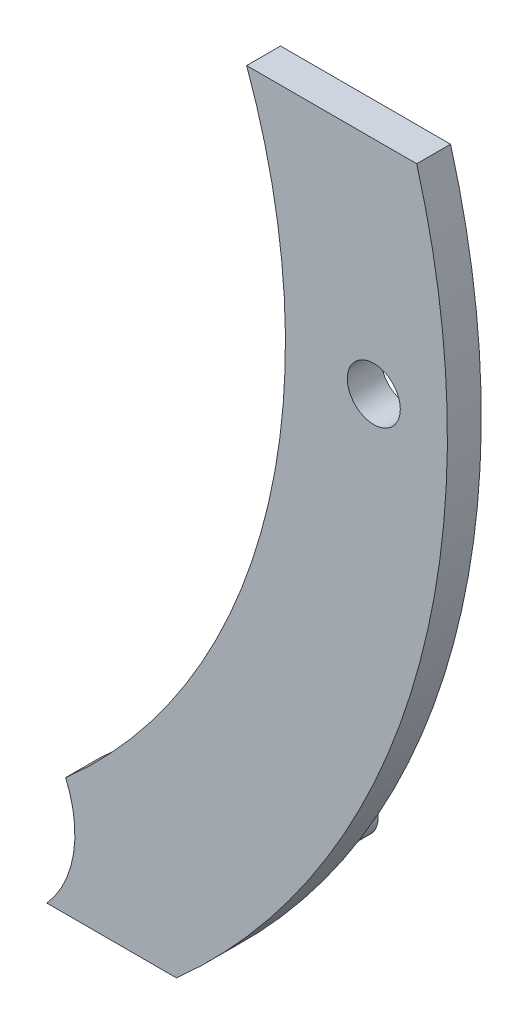
SolidWorks part; units mm, degrees
ref_plane "Front Plane" through (0, 0, 0) normal (0, 0, 1) x (1, 0, 0)
ref_plane "Top Plane" through (0, 0, 0) normal (0, 1, 0) x (1, 0, 0)
ref_plane "Right Plane" through (0, 0, 0) normal (1, 0, 0) x (0, 0, -1)
sketch "Sketch1" plane through (0, 0, 0) normal (0, 0, 1) x (1, 0, 0)
  line L0 (0, 125.7009) -> (0, -111.3832) construction
  line L1 (-141.6644, 0) -> (118.483, 0) construction
  line L2 (0, 69.25) -> (-7.7782, 77.0282) construction
  line L5 (69.0973, -18.82) -> (54.0578, -10.137)
  line L8 (-69.0973, -18.82) -> (-53.8993, -10.9483)
  line L11 (19.8875, 69.25) -> (-21.4021, 69.25) construction
  line L12 (-18.25, 69.25) -> (-18.25, 51.8839)
  line L14 (18.25, 69.25) -> (18.25, 51.8839)
  arc A0 (-75.7772, -43.75) -> (75.7772, -43.75) centre (0, 0) ccw
  circle A18 centre (-7.7782, 77.0282) radius 2.15
  arc A31 (-18.25, 51.8839) -> (-53.8993, -10.9483) centre (0, 0) ccw
  circle A32 centre (0, 0) radius 35
  arc A33 (75.7772, -43.75) -> (69.0973, -18.82) centre (59.9723, -34.625) ccw
  arc A34 (-69.0973, -18.82) -> (-75.7772, -43.75) centre (-59.9723, -34.625) ccw
  arc A36 (54.0578, -10.137) -> (18.25, 51.8839) centre (0, 0) ccw
  circle A38 centre (-50, 0) radius 1.8
  circle A39 centre (-25, 43.3013) radius 1.8
  circle A40 centre (25, 43.3013) radius 1.8
  circle A41 centre (50, 0) radius 1.8
  circle A42 centre (25, -43.3013) radius 1.8
  circle A43 centre (-25, -43.3013) radius 1.8
  arc A44 (18.25, 69.25) -> (-18.25, 69.25) centre (0, 69.25) ccw
  circle A45 centre (7.7782, 77.0282) radius 2.15
  circle A46 centre (7.7782, 61.4718) radius 2.15
  circle A47 centre (-7.7782, 61.4718) radius 2.15
  circle A49 centre (62.8193, -45.2502) radius 2.15
  circle A50 centre (49.3471, -37.472) radius 2.15
  circle A51 centre (57.1252, -23.9998) radius 2.15
  circle A52 centre (70.5974, -31.778) radius 2.15
  circle A54 centre (-70.5974, -31.778) radius 2.15
  circle A55 centre (-57.1252, -23.9998) radius 2.15
  circle A56 centre (-49.3471, -37.472) radius 2.15
  circle A57 centre (-62.8193, -45.2502) radius 2.15
  circle A58 centre (0, 69.25) radius 7.575
  circle A59 centre (59.9723, -34.625) radius 7.575
  circle A60 centre (-59.9723, -34.625) radius 7.575
  point P21 (0, 72.5)
  point P28 (0, 69.25)
  point P40 (0, 0)
  point P41 (0, 0)
  point P42 (0, 72.5)
  point P44 (0, 0)
  point P59 (0, 0)
  point P73 (0, 0)
  point P78 (0, 0)
  dimension "D1" = 175
  dimension "D2" = 70
  dimension "D3" = 18.25
  dimension "D4" = 15.15
  dimension "D5" = 4.3
  dimension "D6" = 11
  dimension "D7" = 3
  dimension "D12" = 110
  dimension "D13" = 3.6
  dimension "D11" = 69.25
  dimension "D8" = 50
  dimension "D15" = 6
  dimension "D9" = 4
  dimension "D10" = 3
extrude "Boss-Extrude1" add sketch "Sketch1" along normal blind 3.175
sketch "Sketch2" plane through (0, 0, 3.175) normal (0, 0, 1) x (1, 0, 0)
  line L0 (0, 93.7487) -> (0, -92.817) construction
  line L1 (-91.7689, 0) -> (95.9614, 0) construction
  line L2 (-35.5093, -64) -> (51.1666, -64) construction
  line L3 (-24, -49) -> (32, -49)
  line L4 (-24, -49) -> (-24, -79)
  line L5 (-24, -79) -> (32, -79)
  line L6 (32, -49) -> (32, -79)
  line L7 (-23.1064, -11.067) -> (5.3725, -70.527)
  line L8 (21.835, -39.1033) -> (32.0072, -56.3108)
  line L9 (0, 0) -> (-23.1064, -11.067) construction
  line L10 (0, 0) -> (25.3854, -3.459) construction
  line L11 (5.3725, -70.527) -> (19, -64) construction
  line L12 (19, -64) -> (32.0072, -56.3108) construction
  line L13 (-19.7204, -33) -> (34.8807, -33) construction
  line L14 (27, -18.9627) -> (27, -48.8294) construction
  line L15 (21, -34.3) -> (39, -34.3)
  line L16 (21, -34.3) -> (21, -37.8)
  line L17 (21, -37.8) -> (39, -37.8)
  line L18 (39, -34.3) -> (39, -37.8)
  line L19 (20.4704, -36.05) -> (41.1675, -36.05) construction
  line L20 (22.7, -29.2) -> (37.3, -29.2)
  line L21 (21, -30.9) -> (21, -31.1)
  line L22 (22.7, -32.8) -> (37.3, -32.8)
  line L23 (39, -30.9) -> (39, -31.1)
  line L24 (-29.2, -43.9) -> (32, -43.9)
  line L25 (-29.2, -43.9) -> (-29.2, -84.1)
  line L26 (-29.2, -84.1) -> (32, -84.1)
  line L27 (32, -43.9) -> (32, -84.1)
  line L28 (25.3854, -3.459) -> (21.0549, -35.2399)
  line L29 (27, -36.05) -> (21.0549, -35.2399) construction
  line L30 (27, -36.05) -> (21.835, -39.1033) construction
  circle A0 centre (23, -81.3) radius 1.35
  circle A1 centre (1, -81.3) radius 1.35
  circle A2 centre (-21, -81.3) radius 1.35
  circle A3 centre (-26.3, -75) radius 1.35
  circle A4 centre (23, -46.7) radius 1.35
  circle A5 centre (1, -46.7) radius 1.35
  circle A6 centre (-21, -46.7) radius 1.35
  circle A7 centre (-26.3, -53) radius 1.35
  circle A8 centre (19, -64) radius 15.11
  circle A9 centre (0, 0) radius 25.62
  circle A10 centre (19, -64) radius 18.5
  arc A13 (21, -30.9) -> (22.7, -29.2) centre (22.7, -30.9) cw
  arc A14 (37.3, -29.2) -> (39, -30.9) centre (37.3, -30.9) cw
  arc A15 (39, -31.1) -> (37.3, -32.8) centre (37.3, -31.1) cw
  arc A16 (22.7, -32.8) -> (21, -31.1) centre (22.7, -31.1) cw
  circle A18 centre (27, -36.05) radius 6
  circle A19 centre (27, -36.05) radius 2.5
  point P47 (21, -36.05)
  point P56 (39, -29.2)
  point P59 (39, -32.8)
  dimension "D4" = 2.7
  dimension "D5" = 9
  dimension "D8" = 2.7
  dimension "D9" = 22
  dimension "D10" = 2.7
  dimension "D11" = 22
  dimension "D12" = 2.7
  dimension "D14" = 58.3
  dimension "D16" = 30.22
  dimension "D17" = 13
  dimension "D18" = 51.24
  dimension "D19" = 37
  dimension "D21" = 5
  dimension "D23" = 1.75
  dimension "D33" = 1.7
  dimension "D34" = 1.7
  dimension "D41" = 12
  dimension "D22" = 3.05
  dimension "D1" = 56
  dimension "D2" = 30
  dimension "D3" = 32
  dimension "D6" = 15
  dimension "D7" = 17.3
  dimension "D13" = 11
  dimension "D15" = 64
  dimension "D20" = 33
  dimension "D25" = 3.5
  dimension "D26" = 27
  dimension "D27" = 6
  dimension "D28" = 12
  dimension "D29" = 3.6
  dimension "D30" = 0.2
  dimension "D31" = 6
  dimension "D32" = 12
  dimension "D36" = 61.2
  dimension "D37" = 40.2
  dimension "D38" = 32
  dimension "D39" = 20.1
sketch "Sketch3" plane through (0, 0, 3.175) normal (0, 0, 1) x (1, 0, 0)
  line L0 (0, 114.667) -> (0, -151.2625) construction
  line L1 (-165.5829, 0) -> (141.148, 0) construction
  line L2 (-42.6786, -64) -> (79.4842, -64) construction
  line L3 (-31.6, -36.5487) -> (-31.6, -93.553) construction
  line L4 (1, -42.7749) -> (1, -93.553) construction
  line L7 (21, -34.3) -> (21, -37.8) construction
  line L8 (21, -37.8) -> (39, -37.8) construction
  line L9 (39, -34.3) -> (39, -37.8) construction
  line L10 (21, -34.3) -> (39, -34.3) construction
  line L15 (21, -34.3) -> (21, -37.8)
  line L16 (21, -37.8) -> (39, -37.8)
  line L17 (39, -34.3) -> (39, -37.8)
  line L18 (21, -34.3) -> (39, -34.3)
  line L19 (59.9723, -34.625) -> (0, 0) construction
  line L20 (59.9723, -34.625) -> (40.6845, -68.0323) construction
  circle A6 centre (-33.85, -49) radius 1.35
  circle A7 centre (-33.85, -75) radius 1.35
  circle A8 centre (41.45, -46.7) radius 1.35
  circle A19 centre (49.9723, -51.9455) radius 5
  circle A20 centre (48.55, -69) radius 1.35
  dimension "D2" = 47.55
  dimension "D3" = 34.85
  dimension "D4" = 2.7
  dimension "D5" = 2.7
  dimension "D8" = 34.85
  dimension "D11" = 40.45
  dimension "D15" = 20
  dimension "D17" = 3.5
  dimension "D14" = 10
  dimension "D16" = 2.7
  dimension "D10" = 5
  dimension "D9" = 2.7
  dimension "D12" = 17.3
  dimension "D1" = 64
  dimension "D6" = 15
  dimension "D7" = 11
  dimension "D13" = 90
  dimension "D18" = 32.6
extrude "Cut-Extrude1" cut sketch "Sketch3" against normal blind 3.175
sketch "Sketch4" plane through (0, 0, 3.175) normal (0, 0, 1) x (1, 0, 0)
  line L0 (0, 99.8873) -> (0, -108.3836) construction
  line L1 (-110.578, 0) -> (106.2745, 0) construction
  line L2 (72.5, 85.3655) -> (72.5, -73.9916) construction
  line L15 (-18.902, 65.232) -> (-24.6423, 79.0902)
  line L16 (-47.0415, -48.9856) -> (-56.173, -60.8859)
  line L29 (0, 0) -> (-45.6571, -59.5015) construction
  line L34 (-44.2727, -70.0174) -> (-35.1412, -58.1171)
  line L35 (-35.1412, -58.1171) -> (-47.0415, -48.9856)
  line L36 (-24.6423, 79.0902) -> (-38.5005, 73.3499)
  line L37 (-38.5005, 73.3499) -> (-32.7602, 59.4917)
  line L38 (-32.7602, 59.4917) -> (-18.902, 65.232)
  line L39 (65.9436, -16.2464) -> (80.8153, -18.2042)
  line L40 (80.8153, -18.2042) -> (82.7731, -3.3326)
  line L41 (82.7731, -3.3326) -> (67.9015, -1.3747)
  line L42 (67.9015, -1.3747) -> (65.9436, -16.2464)
  line L43 (-44.2727, -70.0174) -> (-51.6073, -79.576)
  line L44 (-51.6073, -79.576) -> (-63.5076, -70.4446)
  line L45 (-63.5076, -70.4446) -> (-56.173, -60.8859)
  line L47 (-50.2228, -65.4517) -> (-44.2727, -70.0174) [skipped]
  circle A4 centre (-45.6571, -59.5015) radius 7.5 construction
  point P23 (0, 0)
  point P27 (0, 0)
  point P33 (0, 0)
  dimension "D1" = 52.5
  dimension "D5" = 72.5
  dimension "D7" = 3
  dimension "D3" = 15
  dimension "D4" = 90
  dimension "D2" = 75
extrude "Cut-Extrude2" cut sketch "Sketch4" against normal blind 3.175
sketch "Sketch6" plane through (0, 0, 0) normal (0, 0, 1) x (1, 0, 0)
  line L0 (-30.4163, 69.25) -> (44.9572, 69.25) construction
  circle A0 centre (20, 69.25) radius 7.5
  circle A1 centre (0, 69.25) radius 7.575 construction
  circle A2 centre (-69.9723, -17.3045) radius 7.5
  point P11 (0, 0)
  dimension "D2" = 15
  dimension "D3" = 20
  dimension "D1" = 69.25
  dimension "D4" = 2
extrude "Cut-Extrude5" cut sketch "Sketch6" along normal blind 10
fillet "Fillet1" radius 1.75 4 edges at (21, -37.8, 1.5875) (39, -37.8, 1.5875) (39, -34.3, 1.5875) (21, -34.3, 1.5875)
sketch "Sketch7" plane through (0, 0, 3.175) normal (0, 0, 1) x (1, 0, 0)
  line L0 (-70.8021, 0) -> (80.7932, 0) construction
  line L1 (0, 117.4664) -> (0, -108.5041) construction
  line L2 (-43, 51.6117) -> (-43, -30.4827) construction
  line L7 (-59.7154, 10) -> (-19.0015, 10) construction
  circle A1 centre (-43, 10) radius 1.75
  circle A2 centre (-43, -10) radius 1.75
  dimension "D2" = 3.5
  dimension "D1" = 10
  dimension "D5" = 43
extrude "Cut-Extrude6" cut sketch "Sketch7" against normal blind 10
sketch "Sketch8" plane through (0, 0, 3.175) normal (0, 0, 1) x (1, 0, 0)
  circle A0 centre (0, 0) radius 48
  dimension "D1" = 96
sketch "Sketch9" plane through (0, 0, 0) normal (0, 0, 1) x (1, 0, 0)
  line L0 (-35.5093, -64) -> (51.1666, -64) construction
  line L1 (-35.5093, -64) -> (51.1666, -64)
  point P2 (19, -64)
sketch "Sketch10" plane through (0, 0, 3.175) normal (0, 0, 1) x (1, 0, 0)
  line L0 (22.75, -37.8) -> (37.25, -37.8) construction
  line L1 (37.25, -34.3) -> (22.75, -34.3) construction
  line L2 (29.493, -37.8) -> (37.25, -37.8)
  line L3 (37.25, -34.3) -> (29.493, -34.3)
  line L4 (42.5652, -36.05) -> (13.833, -36.05) construction
  line L5 (66.7692, 0) -> (20.8842, 0) construction
  line L6 (41.3642, 15) -> (52.915, 15)
  line L7 (27.7902, -41.05) -> (36.6046, -41.05)
  circle A0 centre (50, 0) radius 1.8 construction
  circle A1 centre (50, 0) radius 1.8
  arc A3 (37.25, -37.8) -> (39, -36.05) centre (37.25, -36.05) ccw construction
  arc A4 (39, -36.05) -> (37.25, -34.3) centre (37.25, -36.05) ccw construction
  arc A6 (37.25, -37.8) -> (39, -36.05) centre (37.25, -36.05) ccw
  arc A7 (39, -36.05) -> (37.25, -34.3) centre (37.25, -36.05) ccw
  arc A8 (27.7902, -41.05) -> (29.493, -37.8) centre (22.2, -36.05) ccw
  arc A9 (36.6046, -41.05) -> (52.915, 15) centre (0, 0) ccw
  arc A11 (29.0662, -33.0326) -> (41.3642, 15) centre (0, 0) ccw
  arc A12 (29.493, -34.3) -> (29.0662, -33.0326) centre (22.2, -36.05) ccw
  dimension "D1" = 15
  dimension "D2" = 15.05
  dimension "D3" = 110
  dimension "D4" = 44
  dimension "D5" = 15
  dimension "D6" = 5
extrude "Boss-Extrude2" add sketch "Sketch10" along normal blind 2.3
sketch "Sketch11" plane through (0, 0, 0) normal (0, 1, 0) x (1, 0, 0)
  line L1 (83.2287, -3.175) -> (-95.7855, -3.175)
  line L2 (83.2287, -3.175) -> (83.2287, 37.0256)
  line L3 (83.2287, 37.0256) -> (-95.7855, 37.0256)
  line L4 (-95.7855, -3.175) -> (-95.7855, 37.0256)
extrude "Cut-Extrude7" cut sketch "Sketch11" against normal through all both and the other way through all
sketch "Sketch12" plane through (0, 0, 3.175) normal (0, 0, -1) x (-1, 0, 0)
  line L0 (-29.493, -37.8) -> (-37.25, -37.8) construction
  line L1 (-37.25, -34.3) -> (-29.493, -34.3) construction
  line L2 (-29.493, -37.8) -> (-37.25, -37.8)
  line L3 (-37.25, -34.3) -> (-29.493, -34.3)
  arc A0 (-29.493, -34.3) -> (-29.493, -37.8) centre (-22.2, -36.05) ccw
  arc A1 (-39, -36.05) -> (-37.25, -37.8) centre (-37.25, -36.05) ccw construction
  arc A2 (-37.25, -34.3) -> (-39, -36.05) centre (-37.25, -36.05) ccw construction
  arc A3 (-39, -36.05) -> (-37.25, -37.8) centre (-37.25, -36.05) ccw
  arc A4 (-37.25, -34.3) -> (-39, -36.05) centre (-37.25, -36.05) ccw
  point P1 (-72.6672, 1.8523)
extrude "Boss-Extrude3" add sketch "Sketch12" along normal blind 9.5 and the other way blind 2.3
chamfer "Chamfer1" distance 0.5 angle 45 4 edges at (33.3715, -37.8, -6.325) (39, -36.05, -6.325) (33.3715, -34.3, -6.325) (29.7, -36.05, -6.325)
